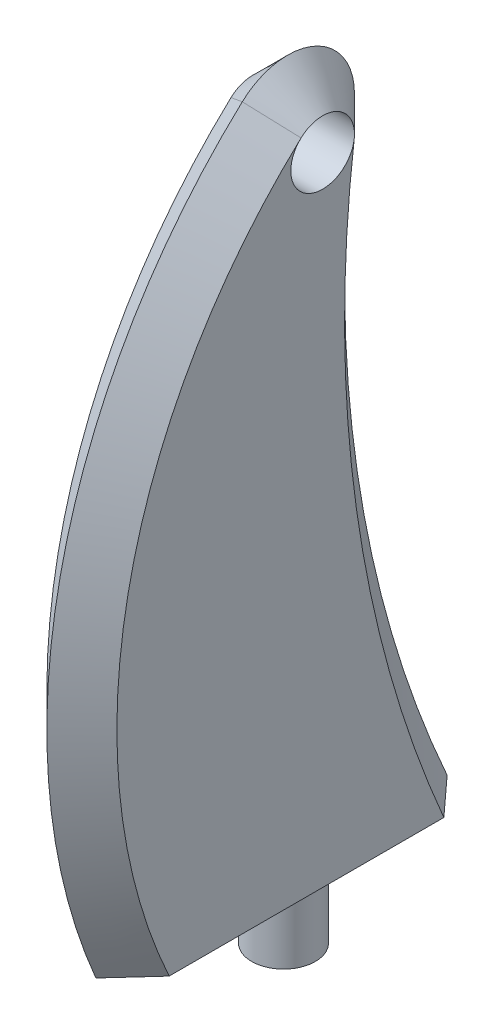
SolidWorks part; units mm, degrees
ref_plane "Front Plane" through (0, 0, 0) normal (0, 0, 1) x (1, 0, 0)
ref_plane "Top Plane" through (0, 0, 0) normal (0, 1, 0) x (1, 0, 0)
ref_plane "Right Plane" through (0, 0, 0) normal (1, 0, 0) x (0, 0, -1)
sketch "Sketch2" plane through (0, 0, 0) normal (1, 0, 0) x (0, 0, -1)
  line L0 (0.6474, -63.4382) -> (0.6474, 36.5618) construction
  line L1 (-34.3526, -63.4382) -> (30.6474, -63.4382)
  arc A0 (15.5277, 34.6701) -> (-9.5308, 47.58) centre (0.6474, 36.5618) ccw
  arc A1 (-34.3526, -63.4382) -> (-9.5308, 47.58) centre (58.3244, -25.8752) cw
  arc A2 (15.5277, 34.6701) -> (30.6474, -63.4382) centre (194.0905, 11.9697) ccw
  dimension "D4" = 30
  dimension "D5" = 180
  dimension "D6" = 100
  dimension "D1" = 30
  dimension "D2" = 35
  dimension "D3" = 100
extrude "Boss-Extrude1" add sketch "Sketch2" against normal mid plane 11 contours A1 A0 A2 L1
sketch "Sketch3" plane through (5.5, 0, 0) normal (1, 0, 0) x (0, 0, -1)
  circle A0 centre (0.6474, 36.5618) radius 5
  dimension "D1" = 10
extrude "Cut-Extrude1" cut sketch "Sketch3" against normal blind 10
chamfer "Chamfer1" distance 10 angle 45 3 edges at (5.5, -4.0557, 39.2661) (5.5, 49.8961, -7.5172) (5.5, -15.447, -16.1908)
chamfer "Chamfer2" distance 10 angle 45 3 edges at (-5.5, -4.0557, 39.2661) (-5.5, 49.8961, -7.5172) (-5.5, -15.447, -16.1908)
sketch "Sketch4" plane through (0, -63.4382, 0) normal (0, -1, 0) x (1, 0, 0)
  circle A0 centre (0, 0) radius 5
  dimension "D1" = 10
extrude "Boss-Extrude2" add sketch "Sketch4" along normal blind 10
